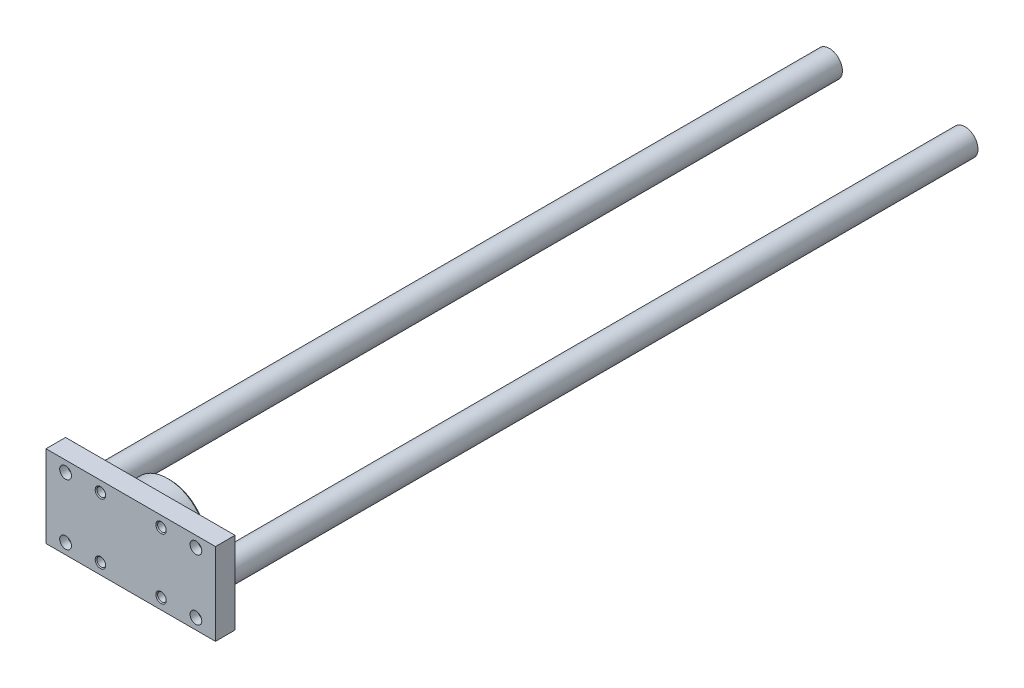
SolidWorks part; units mm, degrees
ref_plane "Front Plane" through (0, 0, 0) normal (0, 0, 1) x (1, 0, 0)
ref_plane "Top Plane" through (0, 0, 0) normal (0, 1, 0) x (1, 0, 0)
ref_plane "Right Plane" through (0, 0, 0) normal (1, 0, 0) x (0, 0, -1)
ref_plane "Plane1" through (0, 0, 89) normal (0, 0, 1) x (1, 0, 0)
sketch "Sketch1" plane through (0, 0, 89) normal (0, 0, 1) x (1, 0, 0)
  line L0 (-65, 31.5) -> (-65, -31.5)
  line L1 (-65, -31.5) -> (65, -31.5)
  line L2 (65, -31.5) -> (65, 31.5)
  line L3 (65, 31.5) -> (-65, 31.5)
extrude "Boss-Extrude1" add sketch "Sketch1" against normal blind 15
ref_plane "Plane2" through (23.25, 0, 0) normal (1, 0, 0) x (0, 0, -1)
sketch "Sketch2" plane through (23.25, 0, 0) normal (1, 0, 0) x (0, 0, -1)
  line L0 (-89, 23.25) -> (-89, 27.25)
  line L1 (-89, 27.25) -> (-88.3235, 26.5735)
  line L2 (-88.3235, 26.5735) -> (-74.6765, 26.5735)
  line L3 (-74.6765, 26.5735) -> (-74, 27.25)
  line L4 (-74, 27.25) -> (-74, 23.25)
  line L5 (-74, 23.25) -> (-89, 23.25)
  line L6 (-74, 23.25) -> (-89, 23.25) construction
revolve "Cut-Revolve1" cut sketch "Sketch2" angle 360 about L6
cosmetic thread "Cosmetic Thread1" parameters "D1"=15, "D2"=8
sketch "Sketch3" plane through (0, 0, 89) normal (0, 0, 1) x (1, 0, 0)
  line L0 (23.25, 23.25) -> (-23.25, 23.25)
  line L1 (23.25, 23.25) -> (23.25, -23.25)
pattern_linear "LPattern1" count 2 spacing 46.5 along (-1, 0, 0) count 2 spacing 46.5 along (0, -1, 0) of "Cut-Revolve1"
cosmetic thread "Cosmetic Thread2" parameters "D1"=15, "D2"=8
cosmetic thread "Cosmetic Thread3" parameters "D1"=15, "D2"=8
cosmetic thread "Cosmetic Thread4" parameters "D1"=15, "D2"=8
ref_plane "Plane3" through (50, 0, 0) normal (1, 0, 0) x (0, 0, -1)
sketch "Sketch4" plane through (50, 0, 0) normal (1, 0, 0) x (0, 0, -1)
  line L0 (-89, 23.25) -> (-89, 27.75)
  line L1 (-89, 27.75) -> (-83, 27.75)
  line L2 (-83, 27.75) -> (-83, 30.75)
  line L3 (-83, 30.75) -> (-74, 30.75)
  line L4 (-74, 30.75) -> (-74, 23.25)
  line L5 (-74, 23.25) -> (-89, 23.25)
  line L6 (-74, 23.25) -> (-89, 23.25) construction
revolve "Cut-Revolve2" cut sketch "Sketch4" angle 360 about L6
sketch "Sketch5" plane through (0, 0, 89) normal (0, 0, 1) x (1, 0, 0)
  line L0 (50, 23.25) -> (-50, 23.25)
  line L1 (50, 23.25) -> (50, -23.25)
pattern_linear "LPattern2" count 2 spacing 100 along (-1, 0, 0) count 2 spacing 46.5 along (0, -1, 0) of "Cut-Revolve2"
sketch "Sketch6" plane through (0, 0, 89) normal (0, 0, 1) x (1, 0, 0)
  circle A0 centre (-52, 0) radius 10
extrude "Boss-Extrude2" add sketch "Sketch6" against normal blind 588
sketch "Sketch7" plane through (0, 0, 89) normal (0, 0, 1) x (1, 0, 0)
  circle A0 centre (52, 0) radius 10
extrude "Boss-Extrude3" add sketch "Sketch7" against normal blind 588
ref_plane "Plane4" through (0, 0, 0) normal (0, 0, 1) x (1, 0, 0)
sketch "Sketch8" plane through (0, 0, 0) normal (1, 0, 0) x (0, 0, -1)
  line L0 (-74, 0) -> (-74, 30)
  line L1 (-74, 30) -> (-60.6, 30)
  line L2 (-60.6, 30) -> (-59, 28.4)
  line L3 (-59, 28.4) -> (-59, 11)
  line L4 (-59, 11) -> (-50, 11)
  line L5 (-50, 11) -> (-49, 10)
  line L6 (-49, 10) -> (-49, 0)
  line L7 (-49, 0) -> (-74, 0)
  line L8 (-49, 0) -> (-74, 0) construction
revolve "Revolve1" add sketch "Sketch8" angle 360 about L8
sketch "Sketch9" plane through (0, 0, 0) normal (1, 0, 0) x (0, 0, -1)
  line L0 (-74, 0) -> (-74, 7.188)
  line L1 (-74, 7.188) -> (-49.812, 7.188)
  line L2 (-49.812, 7.188) -> (-49, 8)
  line L3 (-49, 8) -> (-49, 0)
  line L4 (-49, 0) -> (-74, 0)
  line L5 (-49, 0) -> (-74, 0) construction
revolve "Cut-Revolve3" cut sketch "Sketch9" angle 360 about L5
cosmetic thread "Cosmetic Thread5" parameters "D1"=25, "D2"=16
ref_plane "Plane5" through (0, 0, 54) normal (0, 0, 1) x (1, 0, 0)
ref_plane "Plane6" through (0, 0, 52) normal (0, 0, 1) x (1, 0, 0)
ref_plane "Plane7" through (0, 0, 49) normal (0, 0, 1) x (1, 0, 0)
sketch "Sketch10" plane through (0, 0, 49) normal (0, 0, 1) x (1, 0, 0)
  line L0 (-20, -20) -> (20, -20)
  line L1 (20, -20) -> (20, 20)
  line L2 (20, 20) -> (-20, 20)
  line L3 (-20, 20) -> (-20, -20)
  line L4 (-9, -15) -> (9, -15)
  line L5 (9, -15) -> (9, 15)
  line L6 (9, 15) -> (-9, 15)
  line L7 (-9, 15) -> (-9, -15)
extrude "Cut-Extrude1" cut sketch "Sketch10" along normal blind 10
ref_plane "Plane8" through (0, 0, 42) normal (0, 0, 1) x (1, 0, 0)
ref_plane "FUEHRUNG XY" through (0, 0, 0) normal (0, 0, 1) x (1, 0, 0)
ref_plane "FUEHRUNG XZ" through (0, 0, 0) normal (0, -1, 0) x (-1, 0, 0)
ref_plane "FUEHRUNG YZ" through (0, 0, 0) normal (1, 0, 0) x (0, 0, -1)
ref_axis "FUEHRUNG X" through (-80.9, 0, 0) along (1, 0, 0)
ref_axis "FUEHRUNG Y" through (0, -50, 0) along (0, 1, 0)
ref_axis "FUEHRUNG Z" through (0, 0, 80.9) along (0, 0, -1)
sketch3d "FUEHRUNG"
  point P0 (0, 0, 0)
other "Freeze***"
